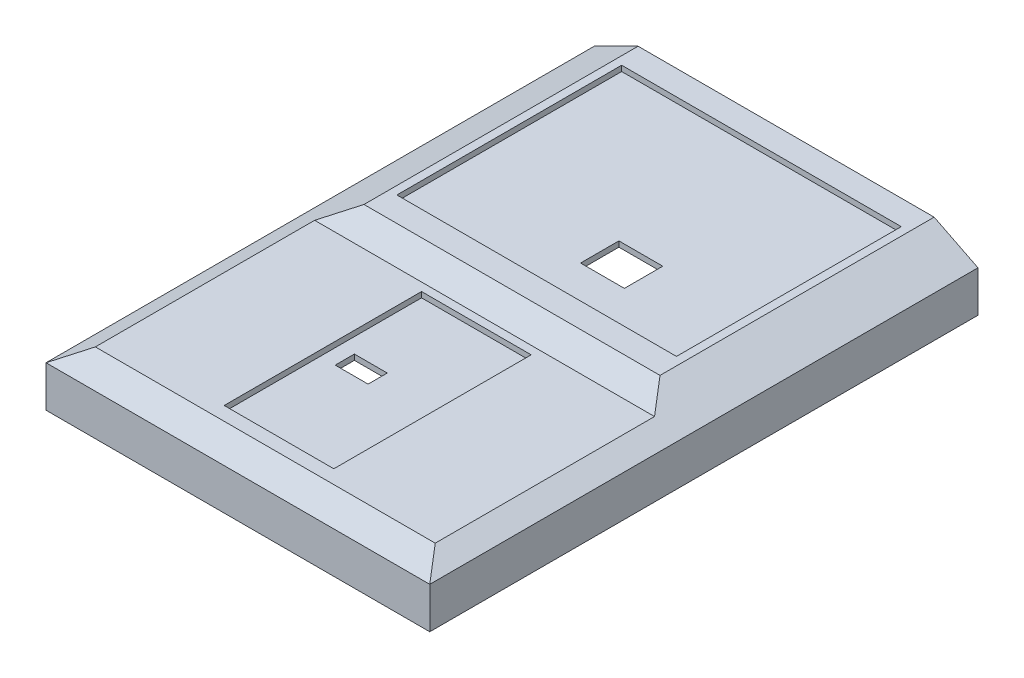
SolidWorks part; units mm, degrees
ref_plane "Ebene vorne" through (0, 0, 0) normal (0, 0, 1) x (1, 0, 0)
ref_plane "Ebene oben" through (0, 0, 0) normal (0, 1, 0) x (1, 0, 0)
ref_plane "Ebene rechts" through (0, 0, 0) normal (1, 0, 0) x (0, 0, -1)
sketch "Skizze1" plane through (0, 0, 0) normal (0, 0, 1) x (1, 0, 0)
  line L1 (-35, -7.5) -> (35, -7.5)
  line L2 (-35, -7.5) -> (-35, 7.5)
  line L3 (-35, 7.5) -> (35, 7.5)
  line L4 (35, -7.5) -> (35, 7.5)
  line L5 (-35, -7.5) -> (35, 7.5) construction
  line L6 (-35, 7.5) -> (35, -7.5) construction
  point P0 (0, 0)
  dimension "D1" = 70
  dimension "D2" = 15
extrude "Aufsatz-Linear austragen1" add sketch "Skizze1" along normal blind 100
sketch "Skizze2" plane through (0, 0, 100) normal (0, 0, 1) x (1, 0, 0)
  line L0 (-35, 7.5) -> (-35, 0)
  line L1 (-35, 7.5) -> (-35, -7.5) construction
  line L2 (-35, 0) -> (-20, 7.5)
  line L3 (35, 7.5) -> (-35, 7.5) construction
  line L4 (-20, 7.5) -> (-35, 7.5)
  dimension "D1" = 15
extrude "Schnitt-Linear austragen1" cut sketch "Skizze2" against normal up to surface (100 mm away) up to face at (0, 0, 0)
ref_plane "Ebene1" through (0, 0, 0) normal (-1, 0, 0) x (0, 0, 1)
mirror "Spiegeln1" about plane through (0, 0, 0) normal (-1, 0, 0) of "Schnitt-Linear austragen1"
sketch "Skizze4" plane through (-35, 0, 0) normal (-1, 0, 0) x (0, 0, 1)
  line L0 (100, 0) -> (95, 2)
  line L1 (95, 2) -> (55, 2)
  line L2 (55, 2) -> (50, 4)
  line L3 (50, 4) -> (0, 4)
  line L5 (0, 7.5) -> (100, 7.5) construction
  line L6 (0, 7.5) -> (100, 7.5)
  line L7 (100, 7.5) -> (100, 0)
  line L8 (0, 0) -> (0, 7.5) construction
  line L9 (0, 4) -> (0, 7.5)
  dimension "D1" = 2
  dimension "D2" = 2
  dimension "D3" = 40
  dimension "D4" = 50
extrude "Schnitt-Linear austragen3" cut sketch "Skizze4" against normal up to surface (70 mm away) up to face at (35, -3.75, 50)
shell "Wandung1" thickness 2 removed face at (0, -7.5, 50)
sketch "Skizze5" plane through (0, 2, 0) normal (0, 1, 0) x (1, 0, 0)
  line L0 (0, 4.125) -> (0, -4.125) construction
  line L1 (-10, -92.5) -> (10, -92.5)
  line L2 (-10, -92.5) -> (-10, -56.5)
  line L3 (-10, -56.5) -> (10, -56.5)
  line L4 (10, -92.5) -> (10, -56.5)
  line L5 (-10, -92.5) -> (10, -56.5) construction
  line L6 (-10, -56.5) -> (10, -92.5) construction
  line L7 (31, -55) -> (-31, -55) construction
  point P0 (0, -74.5)
  dimension "D1" = 36
  dimension "D2" = 20
  dimension "D3" = 1.5
extrude "Schnitt-Linear austragen4" cut sketch "Skizze5" against normal blind 1
sketch "Skizze6" plane through (0, 1, 0) normal (0, 1, 0) x (1, 0, 0)
  line L0 (-10, -56.5) -> (-10, -92.5) construction
  line L1 (-7.25, -71.5) -> (-1.25, -71.5)
  line L2 (-7.25, -71.5) -> (-7.25, -75)
  line L3 (-7.25, -75) -> (-1.25, -75)
  line L4 (-1.25, -71.5) -> (-1.25, -75)
  line L5 (10, -56.5) -> (-10, -56.5) construction
  dimension "D1" = 2.75
  dimension "D2" = 15
  dimension "D3" = 3.5
  dimension "D4" = 6
extrude "Schnitt-Linear austragen5" cut sketch "Skizze6" against normal up to surface (1 mm away) up to face at (0, 0, 74.6148)
sketch "Skizze7" plane through (0, 4, 0) normal (0, 1, 0) x (1, 0, 0)
  line L1 (25.5, -4.5) -> (-25.5, -4.5)
  line L2 (25.5, -4.5) -> (25.5, -45.5)
  line L3 (25.5, -45.5) -> (-25.5, -45.5)
  line L4 (-25.5, -4.5) -> (-25.5, -45.5)
  line L5 (25.5, -4.5) -> (-25.5, -45.5) construction
  line L6 (25.5, -45.5) -> (-25.5, -4.5) construction
  line L7 (27, -50) -> (27, 0) construction
  line L8 (27, 0) -> (-27, 0) construction
  point P0 (0, -25)
  dimension "D1" = 51
  dimension "D2" = 41
  dimension "D3" = 1.5
  dimension "D4" = 4.5
extrude "Schnitt-Linear austragen6" cut sketch "Skizze7" against normal blind 1
sketch "Skizze10" plane through (0, 0, 0) normal (0, 0, -1) x (-1, 0, 0)
  line L0 (7.5, -7.5) -> (-7.5, -7.5)
  line L1 (35, -7.5) -> (-35, -7.5) construction
  line L2 (-7.5, -7.5) -> (-7.5, -5.8)
  line L3 (-7.5, -5.8) -> (-2.5, -5.8)
  line L4 (-2.5, -5.8) -> (-2.5, -4.5)
  line L5 (-2.5, -4.5) -> (2.5, -4.5)
  line L6 (2.5, -4.5) -> (2.5, -5.8)
  line L7 (2.5, -5.8) -> (7.5, -5.8)
  line L8 (7.5, -5.8) -> (7.5, -7.5)
  line L9 (0, -4.125) -> (0, 4.125) construction
  dimension "D1" = 5
  dimension "D2" = 1.3
  dimension "D3" = 2.5
  dimension "D4" = 2.5
  dimension "D5" = 1.7
  dimension "D6" = 1.3
extrude "Schnitt-Linear austragen7" cut sketch "Skizze10" against normal blind 1
sketch "Skizze11" plane through (0, 3, 0) normal (0, 1, 0) x (1, 0, 0)
  line L0 (-25.5, -45.5) -> (25.5, -45.5) construction
  line L1 (9, -38.5) -> (1, -38.5)
  line L2 (9, -38.5) -> (9, -31.5)
  line L3 (9, -31.5) -> (1, -31.5)
  line L4 (1, -38.5) -> (1, -31.5)
  line L5 (25.5, -45.5) -> (25.5, -4.5) construction
  dimension "D1" = 7
  dimension "D2" = 16.5
  dimension "D3" = 8
  dimension "D4" = 7
extrude "Schnitt-Linear austragen8" cut sketch "Skizze11" against normal up to surface (1 mm away) up to face at (0, 2, 25.8074)
